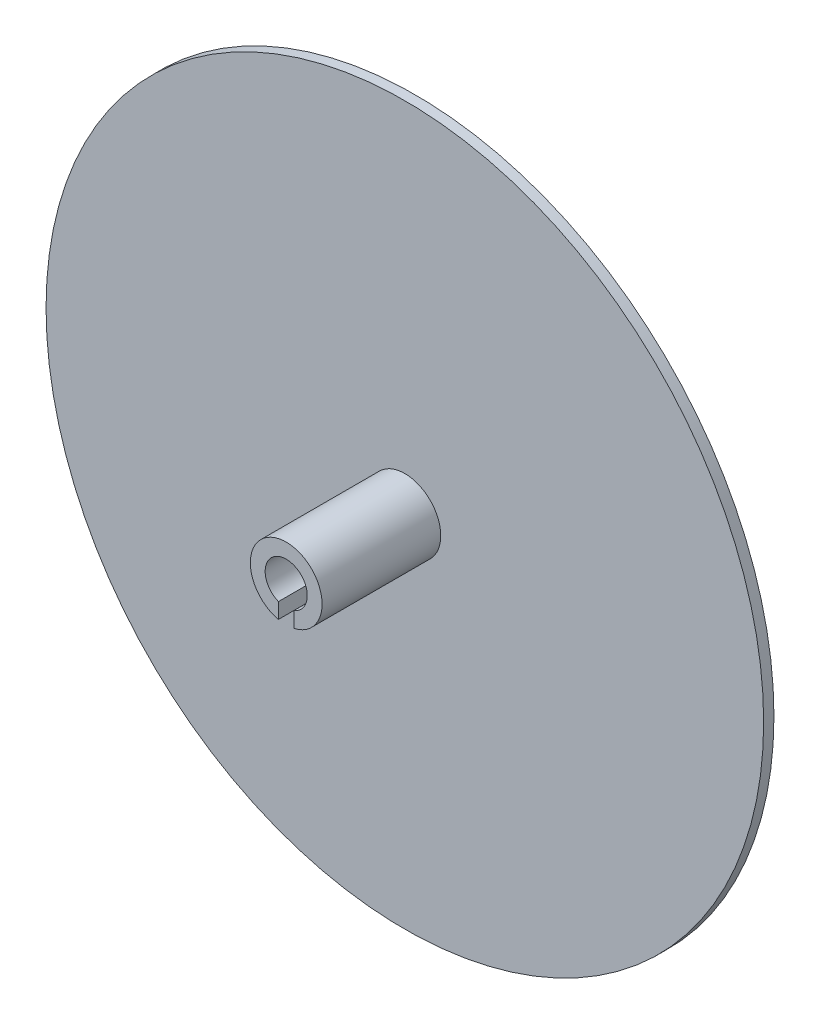
SolidWorks part; units mm, degrees
material "Lega 1060"
ref_plane "Piano frontale" through (0, 0, 0) normal (0, 0, 1) x (1, 0, 0)
ref_plane "Piano superiore" through (0, 0, 0) normal (0, 1, 0) x (1, 0, 0)
ref_plane "Piano destro" through (0, 0, 0) normal (1, 0, 0) x (0, 0, -1)
sketch "Schizzo1" plane through (0, 0, 0) normal (0, 0, 1) x (1, 0, 0)
  circle A0 centre (0, 0) radius 150
  dimension "D1" = 300
extrude "Estrusione-Estrusione1" add sketch "Schizzo1" along normal blind 4.3
sketch "Schizzo2" plane through (0, 0, 4.3) normal (0, 0, 1) x (1, 0, 0)
  circle A0 centre (0, 0) radius 15
  circle A1 centre (0, 0) radius 8.8
  dimension "D1" = 30
  dimension "D2" = 17.6
extrude "Estrusione-Estrusione2" add sketch "Schizzo2" along normal blind 49.6
sketch "Schizzo3" plane through (0, 0, 53.9) normal (0, 0, 1) x (1, 0, 0)
  line L0 (0, 0) -> (0, -15)
  line L2 (-3.25, -25) -> (3.25, -25)
  line L3 (-3.25, -25) -> (-3.25, -5)
  line L4 (-3.25, -5) -> (3.25, -5)
  line L5 (3.25, -25) -> (3.25, -5)
  line L6 (-3.25, -25) -> (3.25, -5) construction
  line L7 (-3.25, -5) -> (3.25, -25) construction
  circle A0 centre (0, 0) radius 15 construction
  circle M5 centre (0, 0) radius 15
  circle M6 centre (0, 0) radius 8.8
  dimension "D1" = 6.5
  dimension "D2" = 20
extrude "Taglio-Estrusione1" cut sketch "Schizzo3" against normal blind 17.25 contours L3 L0 M5 M6 | L5 L0 M5 M6 region at (1.6363, -11.7369, 53.9) region at (-1.6363, -11.7369, 53.9)
